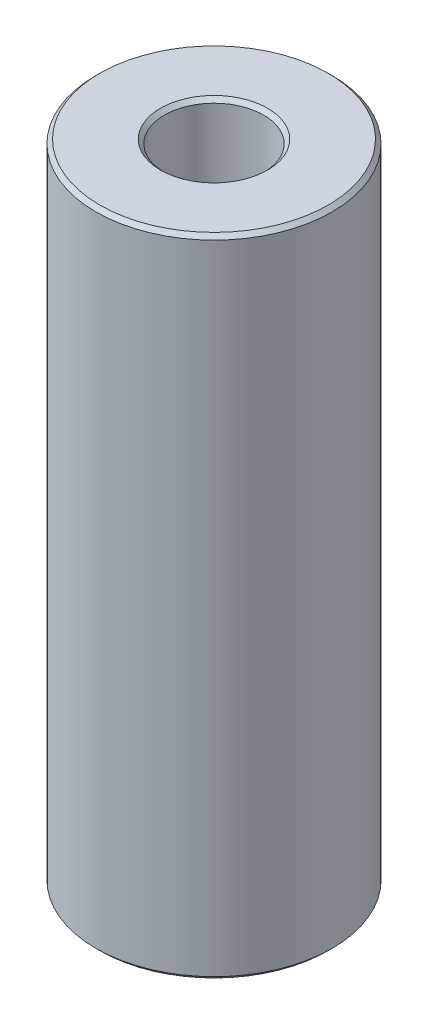
SolidWorks part; units mm, degrees
ref_plane "Front Plane" through (0, 0, 0) normal (0, 0, 1) x (1, 0, 0)
ref_plane "Top Plane" through (0, 0, 0) normal (0, 1, 0) x (1, 0, 0)
ref_plane "Right Plane" through (0, 0, 0) normal (1, 0, 0) x (0, 0, -1)
sketch "Sketch1" plane through (0, 0, 0) normal (0, 1, 0) x (1, 0, 0)
  circle A0 centre (0, 0) radius 60
  dimension "SLEEVE_OD" = 120
extrude "Boss-Extrude1" add sketch "Sketch1" along normal blind 327.9747
sketch "Sketch2" plane through (0, 0, 0) normal (0, 1, 0) x (1, 0, 0)
  circle A0 centre (0, 0) radius 25.2182
  dimension "BORE_D" = 50.4365
extrude "Cut-Extrude1" cut sketch "Sketch2" along normal through all
chamfer "Chamfer1" distance 2.0002 angle 45 4 edges at (0, 327.9747, 25.2182) (0, 0, 25.2182) (0, 0, 60) (0, 327.9747, 60)
